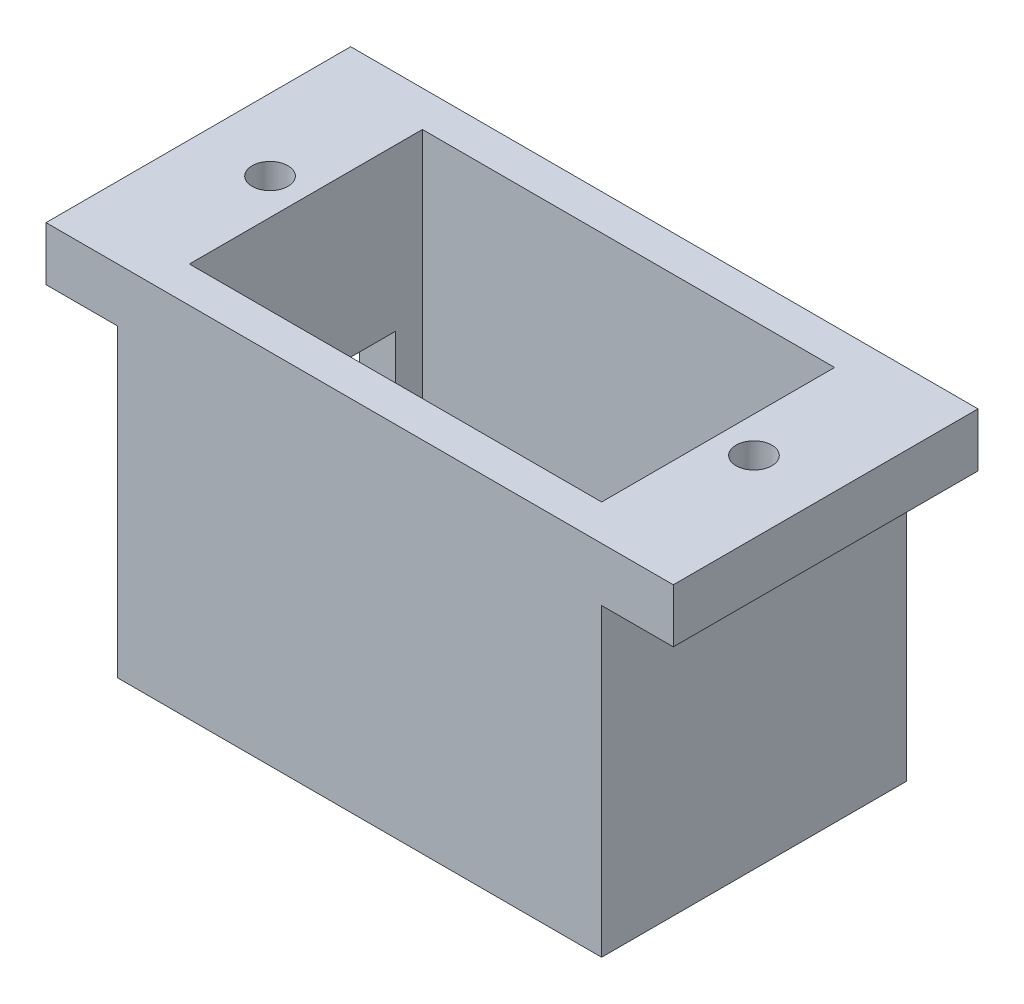
SolidWorks part; units mm, degrees
ref_plane "Front Plane" through (0, 0, 0) normal (0, 0, 1) x (1, 0, 0)
ref_plane "Top Plane" through (0, 0, 0) normal (0, 1, 0) x (1, 0, 0)
ref_plane "Right Plane" through (0, 0, 0) normal (1, 0, 0) x (0, 0, -1)
sketch "Sketch1" plane through (0, 0, 0) normal (0, 1, 0) x (1, 0, 0)
  line L0 (-13.5, 8.5) -> (-13.5, -8.5)
  line L1 (-11.5, 6.5) -> (11.5, 6.5)
  line L2 (-11.5, 6.5) -> (-11.5, -6.5)
  line L3 (-11.5, -6.5) -> (11.5, -6.5)
  line L4 (11.5, 6.5) -> (11.5, -6.5)
  line L5 (-11.5, 6.5) -> (11.5, -6.5) construction
  line L6 (-11.5, -6.5) -> (11.5, 6.5) construction
  line L7 (-13.5, -8.5) -> (13.5, -8.5)
  line L8 (13.5, 8.5) -> (13.5, -8.5)
  line L9 (-13.5, 8.5) -> (13.5, 8.5)
  point P0 (0, 0)
  dimension "D1" = 23
  dimension "D2" = 13
  dimension "D3" = 2
extrude "Boss-Extrude1" add sketch "Sketch1" along normal blind 18
extrude "Boss-Extrude2" add sketch "Sketch1<2>" against normal blind 2 contours L4 L1 L2 L3 | L9 L0 L7 L8 L1 L4 L3 L2 region at (0, 0, -8.1809) region at (0, 0, 0)
sketch "Sketch1<2>" plane through (0, 0, 0) normal (0, 1, 0) x (1, 0, 0) same geometry as "Sketch1"
sketch "Sketch2" plane through (0, 0, 0) normal (0, 1, 0) x (1, 0, 0)
  circle A0 centre (-6, 0) radius 1.5
  circle A1 centre (0, 0) radius 1.5
  circle A2 centre (6, 0) radius 1.5
  dimension "D1" = 3
  dimension "D2" = 6
  dimension "D3" = 6
extrude "Cut-Extrude1" cut sketch "Sketch2" against normal blind 2
sketch "Sketch3" plane through (-13.5, 0, 0) normal (-1, 0, 0) x (0, 0, 1)
  line L0 (-8.5, -2) -> (8.5, -2) construction
  line L1 (-5, 4) -> (5, 4)
  line L2 (-5, 4) -> (-5, 9)
  line L3 (-5, 9) -> (5, 9)
  line L4 (5, 4) -> (5, 9)
  line L5 (-5, 4) -> (5, 9) construction
  line L6 (-5, 9) -> (5, 4) construction
  point P0 (0, 6.5)
  point P7 (0, 0)
  dimension "D1" = 6
  dimension "D2" = 5
  dimension "D3" = 10
extrude "Cut-Extrude2" cut sketch "Sketch3" against normal blind 3
sketch "Sketch4" plane through (0, 18, 0) normal (0, 1, 0) x (1, 0, 0)
  line L0 (13.5, -8.5) -> (13.5, 8.5) construction
  line L1 (-13.5, 8.5) -> (-13.5, -8.5) construction
  line L2 (13.5, -8.5) -> (13.5, 8.5)
  line L3 (-13.5, 8.5) -> (-13.5, -8.5)
  line L4 (-13.5, 8.5) -> (-17.5, 8.5)
  line L5 (-17.5, 8.5) -> (-17.5, -8.5)
  line L6 (-17.5, -8.5) -> (-13.5, -8.5)
  line L7 (13.5, -8.5) -> (17.5, -8.5)
  line L8 (17.5, -8.5) -> (17.5, 8.5)
  line L9 (17.5, 8.5) -> (13.5, 8.5)
  point P9 (13.1105, 8.5)
  dimension "D1" = 4
  dimension "D2" = 4
extrude "Boss-Extrude3" add sketch "Sketch4" against normal blind 3
sketch "Sketch5" plane through (0, 18, 0) normal (0, 1, 0) x (1, 0, 0)
  circle A0 centre (-13.5, 0) radius 1
  circle A1 centre (13.5, 0) radius 1
  dimension "D1" = 2
  dimension "D2" = 2
extrude "Cut-Extrude3" cut sketch "Sketch5" against normal blind 5
